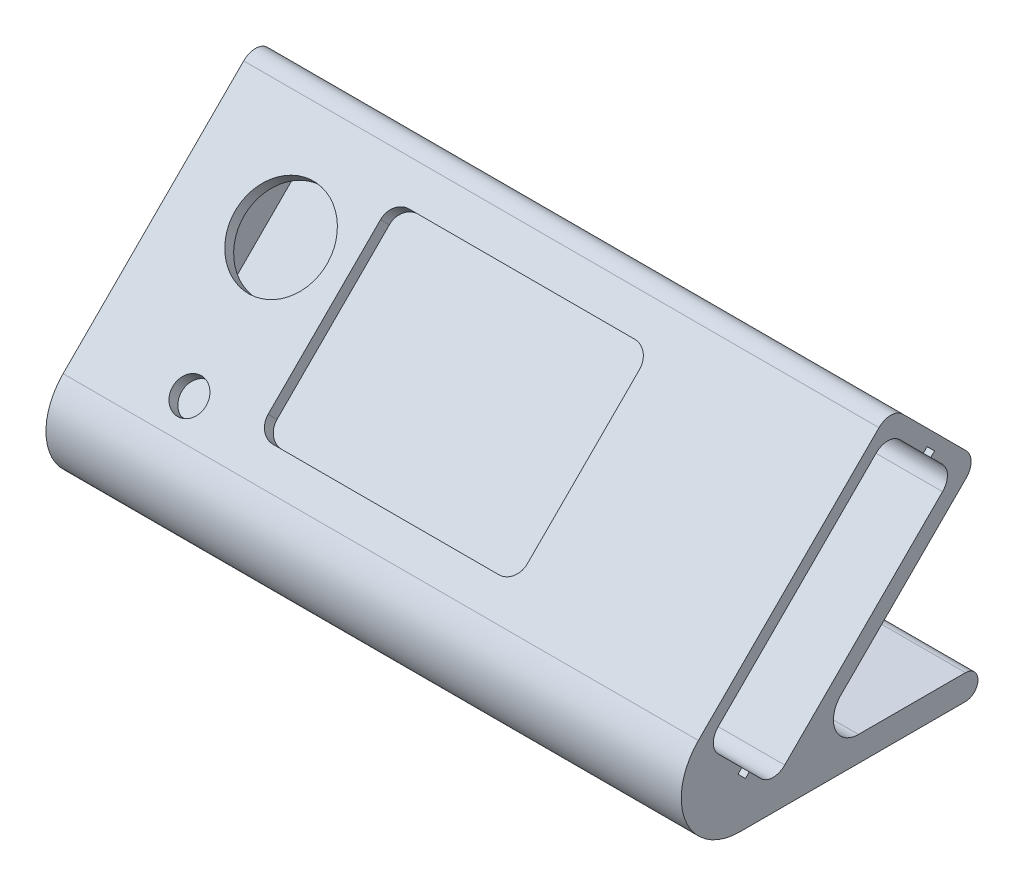
SolidWorks part; units mm, degrees
ref_plane "Front Plane" through (0, 0, 0) normal (0, 0, 1) x (1, 0, 0)
ref_plane "Top Plane" through (0, 0, 0) normal (0, 1, 0) x (1, 0, 0)
ref_plane "Right Plane" through (0, 0, 0) normal (1, 0, 0) x (0, 0, -1)
sketch "Sketch1" plane through (0, 0, 0) normal (1, 0, 0) x (0, 0, -1)
  line L0 (0, 0) -> (21.7082, 21.7082)
  line L1 (0, 0) -> (-2.8284, 2.8284)
  line L2 (-2.8284, 2.8284) -> (-3.288, 2.3688)
  line L3 (-3.288, 2.3688) -> (-4.1719, 3.2527)
  line L4 (-4.1719, 3.2527) -> (-3.7123, 3.7123)
  line L5 (-3.7123, 3.7123) -> (-7.955, 7.955)
  line L6 (-7.955, 7.955) -> (13.7532, 29.6631)
  line L7 (13.7532, 29.6631) -> (17.9959, 25.4205)
  line L8 (17.9959, 25.4205) -> (18.4555, 25.8801)
  line L9 (18.4555, 25.8801) -> (19.3394, 24.9962)
  line L10 (19.3394, 24.9962) -> (18.8798, 24.5366)
  line L11 (18.8798, 24.5366) -> (21.7082, 21.7082)
  line L12 (21.7082, 21.7082) -> (21.4815, 21.6406)
  line L13 (14.1068, 32.138) -> (-10.4298, 7.6014)
  line L15 (3, 0.1716) -> (24.5366, 21.7082)
  line L16 (14.1068, 32.138) -> (24.5366, 21.7082)
  line L17 (-10.4298, 7.6014) -> (-20.8597, -2.8284)
  line L18 (-20.8597, -2.8284) -> (0, -2.8284)
  line L19 (24.5366, -2.8284) -> (24.5366, 0.1716)
  line L20 (24.5366, 0.1716) -> (3, 0.1716)
  line L21 (0, -2.8284) -> (24.5366, -2.8284)
  dimension "D1" = 1.25
  dimension "D2" = 4
  dimension "D3" = 0.65
  dimension "D4" = 6
  dimension "D5" = 32
  dimension "D6" = 2
  dimension "D8" = 1.5
  dimension "D9" = 2
  dimension "D10" = 3
extrude "Boss-Extrude1" add sketch "Sketch1" along normal blind 74.5 contours L18 L21 L19 L20 L15 L16 L13 L17 L10 L11 L0 L1 L2 L3 L4 L5 L6 L7 L8 L9 region at (0, 26.5179, -18.9165)
fillet "Fillet1" radius 7 1 edges at (37.25, -2.8284, 20.8597)
fillet "Fillet2" radius 2 6 edges at (37.25, 0, 0) (37.25, 7.955, 7.955) (37.25, 21.7082, -21.7082) (37.25, 29.6631, -13.7532) (37.25, 21.7082, -24.5366) (37.25, 32.138, -14.1068)
fillet "Fillet3" radius 1.5 2 edges at (37.25, -2.8284, -24.5366) (37.25, 0.1716, -24.5366)
fillet "Fillet4" radius 3 1 edges at (37.25, 0.1716, -3)
sketch "Sketch3" plane through (0, 9.0156, 9.0156) normal (0, 0.7071, 0.7071) x (1, 0, 0)
  line L0 (0, 26.85) -> (74.5, 26.85) construction
  line L1 (0, 30.7) -> (0, 0.1495) construction
  line L2 (74.5, 30.7) -> (74.5, 0.1495) construction
  line L3 (74.5, 31.35) -> (0, 31.35) construction
  line L4 (0, 3.85) -> (74.5, 3.85) construction
  line L5 (11, 32.7) -> (11, -6.8505) construction
  line L6 (0, 32.7) -> (74.5, 32.7) construction
  line L7 (0, -6.8505) -> (74.5, -6.8505) construction
  line L8 (0, 3.85) -> (74.5, 3.85) construction
  line L9 (74.5, -0.65) -> (0, -0.65) construction
  line L10 (0, 19.35) -> (74.5, 19.35) construction
  line L11 (19, 32.7) -> (19, -6.8505) construction
  line L12 (50, 32.7) -> (50, -6.8505) construction
  line L13 (19, 26.85) -> (50, 26.85)
  line L14 (50, 26.85) -> (50, 3.85)
  line L15 (50, 3.85) -> (19, 3.85)
  line L16 (19, 3.85) -> (19, 26.85)
  circle A0 centre (11, 19.35) radius 5.5
  circle A1 centre (11, 3.85) radius 2
  dimension "D8" = 11
  dimension "D9" = 4
  dimension "D1" = 4.5
  dimension "D2" = 23
  dimension "D3" = 11
  dimension "D4" = 4.5
  dimension "D5" = 12
  dimension "D6" = 19
  dimension "D7" = 31
extrude "Cut-Extrude1" cut sketch "Sketch3" against normal up to vertex (1.5 mm away) up to point (0, 28.2489, -12.339)
fillet "Fillet5" radius 2 4 edges at (50, 11.2076, 5.7629) (50, 27.4711, -10.5005) (19, 11.2076, 5.7629) (19, 27.4711, -10.5005)
sketch "Sketch4" plane through (0, 0, 0) normal (-1, 0, 0) x (0, 0, 1)
  line L5 (-23.0366, -2.8284) -> (3.9602, -2.8284)
  line L6 (8.9099, 9.1213) -> (-12.6926, 30.7238)
  line L7 (-15.521, 30.7238) -> (-23.1224, 23.1224)
  line L8 (-23.1224, 20.294) -> (-8.1213, 5.2929)
  line L9 (-10.2426, 0.1716) -> (-23.0366, 0.1716)
  line L10 (-23.0366, -2.8284) -> (3.9602, -2.8284)
  line L11 (8.9099, 9.1213) -> (-12.6926, 30.7238)
  line L12 (-15.521, 30.7238) -> (-23.1224, 23.1224)
  line L13 (-23.1224, 20.294) -> (-8.1213, 5.2929)
  line L14 (-10.2426, 0.1716) -> (-23.0366, 0.1716)
  arc A6 (-23.0366, 0.1716) -> (-24.5366, -1.3284) centre (-23.0366, -1.3284) ccw
  arc A7 (-24.5366, -1.3284) -> (-23.0366, -2.8284) centre (-23.0366, -1.3284) ccw
  arc A8 (3.9602, -2.8284) -> (8.9099, 9.1213) centre (3.9602, 4.1716) ccw
  arc A9 (-12.6926, 30.7238) -> (-15.521, 30.7238) centre (-14.1068, 29.3096) ccw
  arc A10 (-23.1224, 23.1224) -> (-23.1224, 20.294) centre (-21.7082, 21.7082) ccw
  arc A11 (-10.2426, 0.1716) -> (-8.1213, 5.2929) centre (-10.2426, 3.1716) ccw
  arc A12 (-23.0366, 0.1716) -> (-24.5366, -1.3284) centre (-23.0366, -1.3284) ccw
  arc A13 (-24.5366, -1.3284) -> (-23.0366, -2.8284) centre (-23.0366, -1.3284) ccw
  arc A14 (3.9602, -2.8284) -> (8.9099, 9.1213) centre (3.9602, 4.1716) ccw
  arc A15 (-12.6926, 30.7238) -> (-15.521, 30.7238) centre (-14.1068, 29.3096) ccw
  arc A16 (-23.1224, 23.1224) -> (-23.1224, 20.294) centre (-21.7082, 21.7082) ccw
  arc A17 (-10.2426, 0.1716) -> (-8.1213, 5.2929) centre (-10.2426, 3.1716) ccw
  dimension "D1" = 0
extrude "Boss-Extrude3" add sketch "Sketch4" along normal blind 1.5
